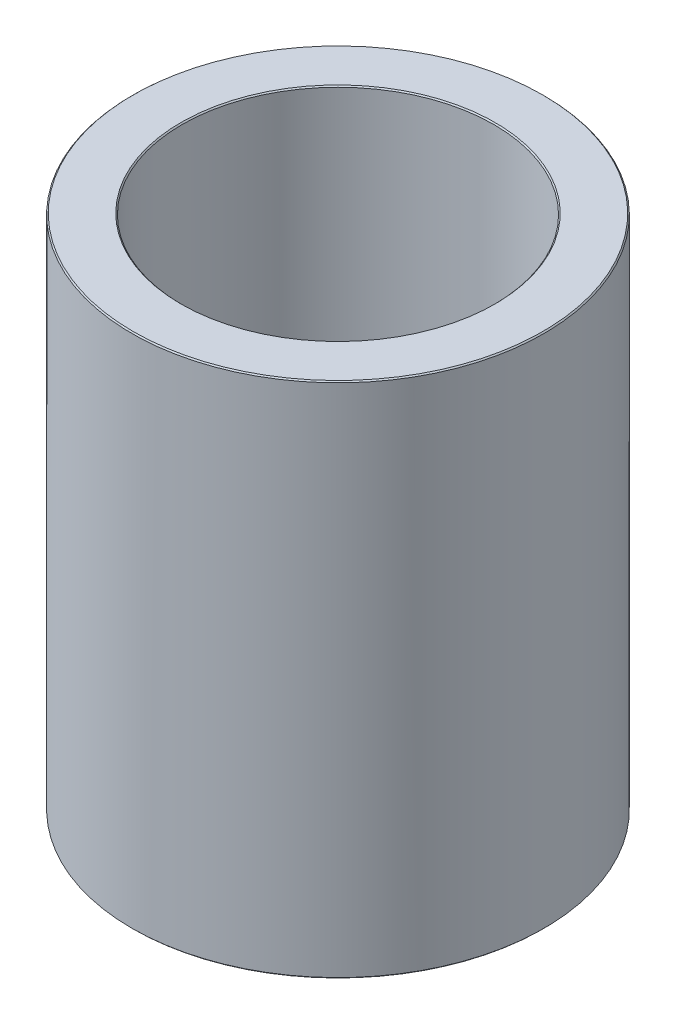
SolidWorks part; units mm, degrees
ref_plane "Front Plane" through (0, 0, 0) normal (0, 0, 1) x (1, 0, 0)
ref_plane "Top Plane" through (0, 0, 0) normal (0, 1, 0) x (1, 0, 0)
ref_plane "Right Plane" through (0, 0, 0) normal (1, 0, 0) x (0, 0, -1)
sketch "Sketch1" plane through (0, 0, 0) normal (0, 1, 0) x (1, 0, 0)
  circle A0 centre (0, 0) radius 45
  dimension "SLEEVE_OD" = 90
extrude "Boss-Extrude1" add sketch "Sketch1" along normal blind 113.0192
sketch "Sketch2" plane through (0, 0, 0) normal (0, 1, 0) x (1, 0, 0)
  circle A0 centre (0, 0) radius 34.0678
  dimension "BORE_D" = 68.1357
extrude "Cut-Extrude1" cut sketch "Sketch2" along normal through all
chamfer "Chamfer1" distance 0.256 angle 45 4 edges at (0, 113.0192, 34.0678) (0, 0, 34.0678) (0, 0, 45) (0, 113.0192, 45)
